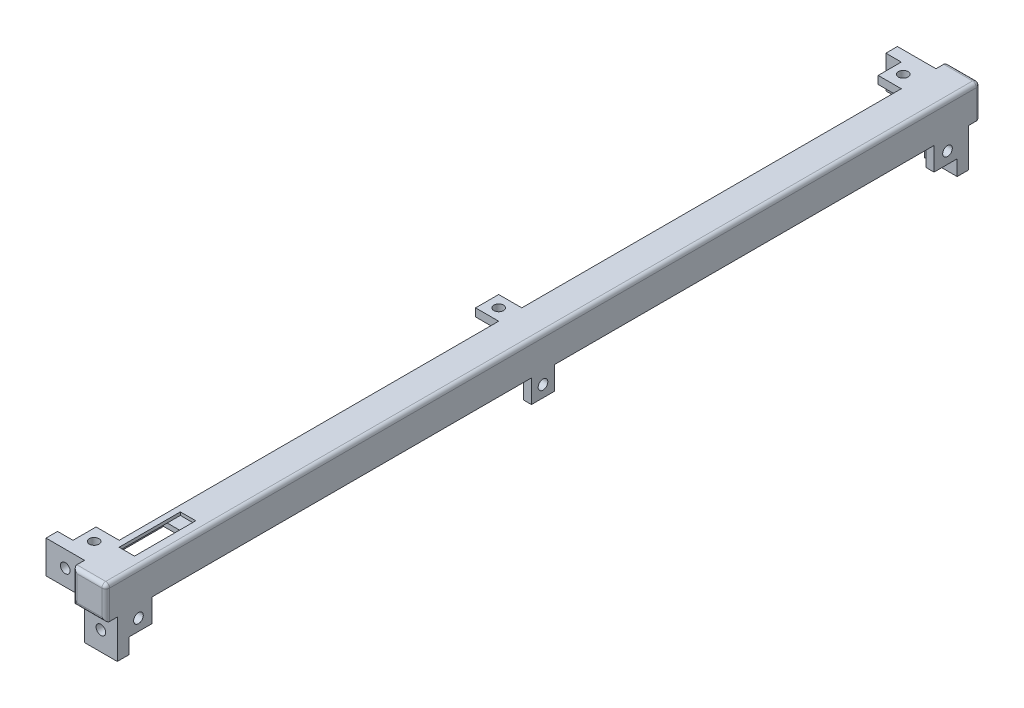
SolidWorks part; units mm, degrees
material "Liga 6061"
ref_plane "Plano frontal" through (0, 0, 0) normal (0, 0, 1) x (1, 0, 0)
ref_plane "Plano superior" through (0, 0, 0) normal (0, 1, 0) x (1, 0, 0)
ref_plane "Plano direito" through (0, 0, 0) normal (1, 0, 0) x (0, 0, -1)
sketch "Esboço1" plane through (0, 0, 0) normal (0, 0, 1) x (1, 0, 0)
  line L1 (4.25, -4.25) -> (-4.25, -4.25)
  line L2 (4.25, -4.25) -> (4.25, 4.25)
  line L3 (4.25, 4.25) -> (-4.25, 4.25)
  line L4 (-4.25, -4.25) -> (-4.25, 4.25)
  line L5 (4.25, -4.25) -> (-4.25, 4.25) construction
  line L6 (4.25, 4.25) -> (-4.25, -4.25) construction
  point P0 (0, 0)
  dimension "D1" = 8.5
  dimension "D2" = 8.5
extrude "Ressalto-extrusão1" add sketch "Esboço1" along normal blind 227
fillet "Filete1" radius 1 1 edges at (4.25, 4.25, 113.5)
fillet "Filete2" radius 1 5 edges at (0, -4.25, 227) (-4.25, 0, 227) (-0.5, 4.25, 227) (3.9571, 3.9571, 227) (4.25, -0.5, 227)
fillet "Filete3" radius 1 5 edges at (-4.25, 0, 0) (0, -4.25, 0) (4.25, -0.5, 0) (3.9571, 3.9571, 0) (-0.5, 4.25, 0)
sketch "Esboço2" plane through (-4.25, 0, 0) normal (-1, 0, 0) x (0, 0, 1)
  line L0 (6, 4.25) -> (6, 2.2) construction
  line L1 (226, 4.25) -> (1, 4.25) construction
  line L2 (1, 4.25) -> (1, -4.25) construction
  line L3 (226, -4.25) -> (226, 4.25) construction
  line L5 (221, 2.2) -> (221, -4.25) construction
  line L6 (226, -4.25) -> (1, -4.25) construction
  line L7 (221, -4.25) -> (6, 2.2) construction
  line L8 (6, 2.2) -> (6, -4.25) construction
  line L9 (6, -4.25) -> (221, 2.2) construction
  line L11 (6, 2.2) -> (221, 2.2)
  line L12 (6, 2.2) -> (6, -4.25)
  line L13 (6, -4.25) -> (221, -4.25)
  line L14 (221, 2.2) -> (221, -4.25)
  line L15 (6, 2.2) -> (221, -4.25) construction
  line L16 (6, -4.25) -> (221, 2.2) construction
  point P10 (113.5, -1.025)
  dimension "D1" = 5
  dimension "D2" = 5
extrude "Corte-extrusão2" cut sketch "Esboço2" against normal blind 3.6
sketch "Esboço3" plane through (-4.25, 0, 0) normal (-1, 0, 0) x (0, 0, 1)
  line L1 (226, 4.25) -> (1, 4.25) construction
  line L4 (3, 4.25) -> (3, -4.25)
  line L5 (1, 4.25) -> (1, -4.25) construction
  line L6 (6, -4.25) -> (1, -4.25) construction
  line L7 (3, 4.25) -> (6, 4.25)
  line L8 (6, 4.25) -> (6, -4.25)
  line L9 (224, 4.25) -> (221, 4.25)
  line L10 (226, -4.25) -> (221, -4.25) construction
  line L12 (221, 4.25) -> (221, -4.25)
  line L13 (224, 4.25) -> (224, -4.25)
  line L14 (221, -4.25) -> (224, -4.25)
  line L15 (6, -4.25) -> (3, -4.25)
  line L16 (226, -4.25) -> (226, 4.25) construction
  dimension "D1" = 2
  dimension "D2" = 2
extrude "Ressalto-extrusão3" add sketch "Esboço3" along normal blind 10
sketch "Esboço4" plane through (0, -4.25, 0) normal (0, -1, 0) x (1, 0, 0)
  line L0 (-4.25, 224) -> (4.25, 224)
  line L3 (4.25, 226) -> (4.25, 1) construction
  line L4 (-4.25, 224) -> (-4.25, 221)
  line L5 (-4.25, 221) -> (4.25, 221)
  line L6 (4.25, 221) -> (4.25, 224)
  line L7 (-4.25, 3) -> (4.25, 3)
  line L8 (4.25, 6) -> (-4.25, 6)
  line L9 (4.25, 3) -> (4.25, 6)
  line L10 (-0.65, 6) -> (-14.25, 6) construction
  line L12 (-4.25, 6) -> (-4.25, 3)
extrude "Ressalto-extrusão4" add sketch "Esboço4" along normal blind 10
sketch "Esboço5" plane through (-4.25, 0, 0) normal (-1, 0, 0) x (0, 0, 1)
  line L0 (6, 4.25) -> (12, 4.25)
  line L1 (221, 4.25) -> (6, 4.25) construction
  line L2 (12, 4.25) -> (12, 2.2)
  line L3 (221, 2.2) -> (6, 2.2) construction
  line L4 (221, 2.2) -> (6, 2.2) construction
  line L5 (221, 4.25) -> (215, 4.25)
  line L6 (113.5, 2.2) -> (113.5, 4.25) construction
  line L7 (116.5, 4.25) -> (110.5, 4.25)
  line L8 (110.5, 4.25) -> (110.5, 2.2)
  line L9 (110.5, 2.2) -> (116.5, 2.2)
  line L10 (116.5, 4.25) -> (116.5, 2.2)
  line L11 (12, 2.2) -> (6, 2.2)
  line L12 (6, 2.2) -> (6, 4.25)
  line L13 (215, 4.25) -> (215, 2.2)
  line L14 (215, 2.2) -> (221, 2.2)
  line L15 (221, 2.2) -> (221, 4.25)
extrude "Ressalto-extrusão5" add sketch "Esboço5" along normal blind 6
sketch "Esboço6" plane through (0, -4.25, 0) normal (0, -1, 0) x (1, 0, 0)
  line L0 (4.25, 6) -> (4.25, 12)
  line L1 (4.25, 221) -> (4.25, 6) construction
  line L2 (4.25, 12) -> (2.2, 12)
  line L3 (2.2, 12) -> (2.2, 6)
  line L4 (4.25, 6) -> (-0.65, 6) construction
  line L5 (2.2, 6) -> (4.25, 6)
  line L6 (-0.65, 113.5) -> (4.25, 113.5) construction
  line L7 (-0.65, 6) -> (-0.65, 221) construction
  line L8 (4.25, 113.5) -> (4.25, 116.5)
  line L9 (4.25, 116.5) -> (2.2, 116.5)
  line L10 (2.2, 116.5) -> (2.2, 110.5)
  line L11 (2.2, 110.5) -> (4.25, 110.5)
  line L12 (4.25, 221) -> (4.25, 215)
  line L14 (4.25, 215) -> (2.2, 215)
  line L15 (2.2, 215) -> (2.2, 221)
  line L16 (-0.65, 221) -> (4.25, 221) construction
  line L17 (4.25, 110.5) -> (4.25, 113.5)
  line L18 (2.2, 221) -> (4.25, 221)
extrude "Ressalto-extrusão6" add sketch "Esboço6" along normal blind 6
extrude "Ressalto-extrusão7" add sketch "Esboço6<2>" along normal blind 6
sketch "Esboço6<2>" plane through (0, -4.25, 0) normal (0, -1, 0) x (1, 0, 0) same geometry as "Esboço6"
sketch "Esboço7" plane through (0, 0, 224) normal (0, 0, 1) x (1, 0, 0)
  line L0 (-14.25, 4.25) -> (-4.25, -4.25) construction
  line L1 (-14.25, -4.25) -> (-4.25, 4.25) construction
  line L2 (-4.25, -4.25) -> (4.25, -14.25) construction
  line L3 (-4.25, -14.25) -> (4.25, -4.25) construction
  circle A0 centre (-9.25, 0) radius 1.25
  circle A1 centre (0, -9.25) radius 1.25
extrude "Corte-extrusão3" cut sketch "Esboço7" against normal blind 250
sketch "Esboço8" plane through (4.25, 0, 0) normal (1, 0, 0) x (0, 0, -1)
  line L0 (-215, -4.25) -> (-221, -4.25) construction
  line L1 (-221, -4.25) -> (-221, -10.25) construction
  line L2 (-116.5, -10.25) -> (-110.5, -4.25) construction
  line L3 (-116.5, -4.25) -> (-110.5, -10.25) construction
  line L5 (-12, -4.25) -> (-6, -4.25) construction
  line L6 (-221, -7.25) -> (-218.5, -7.25) construction
  line L7 (-6, -4.25) -> (-6, -10.25) construction
  line L8 (-6, -7.25) -> (-8.5, -7.25) construction
  circle A0 centre (-218.5, -7.25) radius 1.25
  circle A1 centre (-113.5, -7.25) radius 1.25
  circle A2 centre (-8.5, -7.25) radius 1.25
extrude "Corte-extrusão4" cut sketch "Esboço8" against normal blind 5
sketch "Esboço9" plane through (0, 4.25, 0) normal (0, 1, 0) x (1, 0, 0)
  line L0 (-4.25, -215) -> (-4.25, -221) construction
  line L1 (-4.25, -221) -> (-10.25, -221) construction
  line L2 (-10.25, -110.5) -> (-4.25, -116.5) construction
  line L3 (-10.25, -116.5) -> (-4.25, -110.5) construction
  line L4 (-10.25, -6) -> (-4.25, -6) construction
  line L7 (-4.25, -6) -> (-4.25, -12) construction
  line L8 (-7.25, -221) -> (-7.25, -218.5) construction
  line L9 (-7.25, -6) -> (-7.25, -8.5) construction
  circle A0 centre (-7.25, -218.5) radius 1.25
  circle A1 centre (-7.25, -113.5) radius 1.25
  circle A2 centre (-7.25, -8.5) radius 1.25
extrude "Corte-extrusão5" cut sketch "Esboço9" against normal blind 5
sketch "Esboço11" plane through (0, -4.25, 0) normal (0, -1, 0) x (1, 0, 0)
  line L3 (-0.65, 204.0789) -> (-0.65, 217.0789)
  line L6 (2.25, 204.0789) -> (-0.65, 204.0789)
  line L15 (2.25, 217.0789) -> (2.25, 204.0789)
  line L16 (-0.65, 217.0789) -> (2.25, 217.0789)
extrude "Corte-extrusão6" cut sketch "Esboço11" against normal blind 7.7
sketch "Esboço15" plane through (2.25, 0, 0) normal (-1, 0, 0) x (0, 0, 1)
  line L0 (204.0789, 3.45) -> (217.0789, 3.45)
  line L1 (217.0789, 3.45) -> (217.0789, -4.25)
  line L2 (217.0789, -4.25) -> (204.0789, -4.25)
  line L3 (204.0789, -4.25) -> (204.0789, 3.45)
extrude "Corte-extrusão10" cut sketch "Esboço15" along normal blind 5.9
sketch "Esboço16" plane through (0, 3.45, 0) normal (0, -1, 0) x (1, 0, 0)
  line L0 (-2.7, 204.0789) -> (1.3, 204.0789)
  line L3 (-3.65, 217.0789) -> (2.25, 217.0789) construction
  line L4 (-2.7, 216.5789) -> (1.3, 216.5789)
  line L5 (-2.7, 216.5789) -> (-2.7, 204.0789)
  line L6 (1.3, 216.5789) -> (1.3, 204.0789)
  line L7 (-3.65, 216.5789) -> (2.25, 216.5789) construction
  line L8 (-0.7, 204.0789) -> (-0.7, 217.0789) construction
  dimension "D1" = 0.5
extrude "Corte-extrusão12" cut sketch "Esboço16" against normal blind 5.9
sketch "Esboço17" plane through (0, 4.25, 0) normal (0, 1, 0) x (1, 0, 0)
  line L0 (-2.7, -204.0789) -> (-2.7, -200.677)
  line L1 (-2.7, -200.677) -> (1.3, -200.677)
  line L2 (1.3, -204.0789) -> (1.3, -200.677)
  line L3 (-2.7, -204.0789) -> (1.3, -204.0789)
extrude "Corte-extrusão14" cut sketch "Esboço17" against normal blind 0.8
